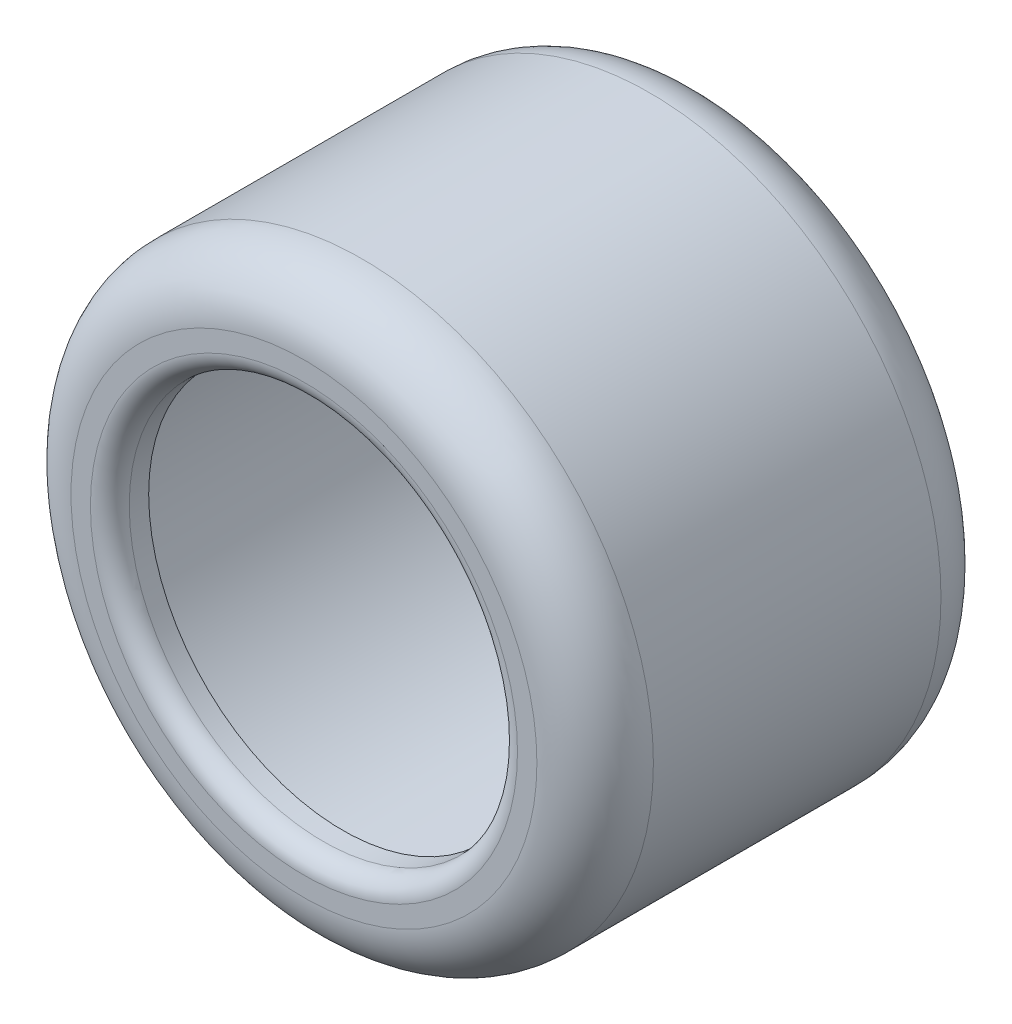
SolidWorks part; units mm, degrees
ref_plane "Alzado" through (0, 0, 0) normal (0, 0, 1) x (1, 0, 0)
ref_plane "Planta" through (0, 0, 0) normal (0, 1, 0) x (1, 0, 0)
ref_plane "Vista lateral" through (0, 0, 0) normal (1, 0, 0) x (0, 0, -1)
sketch "Croquis1" plane through (0, 0, 0) normal (0, 0, 1) x (1, 0, 0)
  circle A0 centre (0, 0) radius 10
  dimension "D1" = 20
extrude "Extruir-Lámina1" add sketch "Croquis1" along normal blind 20.8152 thin thin type one direction wall 5
fillet "Redondeo1" radius 3 2 edges at (15, 0, 0) (15, 0, 20.8152)
fillet "Redondeo2" radius 1 2 edges at (10, 0, 0) (10, 0, 20.8152)
shell "Vaciado1" thickness 2 removed face at (10, 0, 1)
scale "Escala4" scale about centroid uniform scaling yes scale factor 4
scale "Escala6" scale about centroid uniform scaling yes scale factor 2
